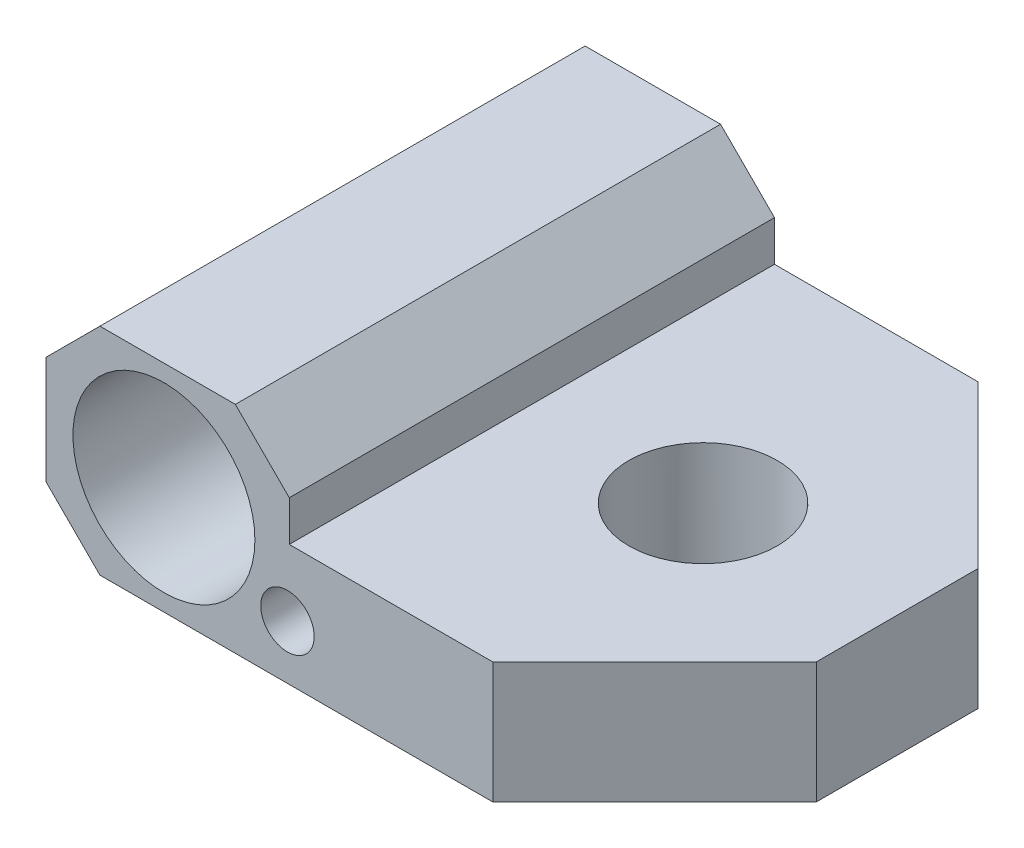
SolidWorks part; units mm, degrees
material "2024 Alloy"
ref_plane "Front Plane" through (0, 0, 0) normal (0, 0, 1) x (1, 0, 0)
ref_plane "Top Plane" through (0, 0, 0) normal (0, 1, 0) x (1, 0, 0)
ref_plane "Right Plane" through (0, 0, 0) normal (1, 0, 0) x (0, 0, -1)
sketch "Sketch1" plane through (0, 0, 0) normal (0, 1, 0) x (1, 0, 0)
  line L0 (0, 0) -> (0, 9) construction
  line L1 (-15.375, 9) -> (7.2, 9)
  line L2 (-15.375, 9) -> (-15.375, -9)
  line L3 (-15.375, -9) -> (7.2, -9)
  line L4 (7.2, 9) -> (7.2, -9)
  line L5 (-11, -9) -> (-11, 9) construction
  line L6 (-14.375, -9) -> (-14.375, 9) construction
  line L7 (-7.625, -9) -> (-7.625, 9) construction
  line L8 (-4, -9) -> (-4, 9) construction
  line L9 (-5.981, -9) -> (-5.981, 9) construction
  line L10 (0, 0) -> (7.2, 0) construction
  line L11 (7.2, 0) -> (3.6, 6.2354) construction
  line L12 (3.6, 6.2354) -> (-3.6, 6.2354) construction
  line L13 (-3.6, 6.2354) -> (-7.2, 0) construction
  line L14 (-7.2, 0) -> (-3.6, -6.2354) construction
  line L15 (-3.6, -6.2354) -> (3.6, -6.2354) construction
  line L16 (3.6, -6.2354) -> (7.2, 0) construction
  circle A0 centre (0, 0) radius 2.75
  circle A1 centre (0, 0) radius 6.2354 construction
  dimension "D1" = 5.5
  dimension "D4" = 14.4
  dimension "D2" = 6.75
  dimension "D3" = 11
  dimension "D5" = 1.981
  dimension "D6" = 1
  dimension "D7" = 18
  dimension "D8" = 4
extrude "Boss-Extrude1" add sketch "Sketch1" along normal blind 4 and the other way blind 4
cosmetic thread "Cosmetic Thread1" parameters "D2"=7.9375
sketch "Sketch3" plane through (0, 0, 9) normal (0, 0, 1) x (1, 0, 0)
  line L2 (-6.4174, -2) -> (-6.4174, -4) construction
  line L3 (-15.375, -4) -> (7.2, -4) construction
  line L4 (-11, 0) -> (-6.4174, -2) construction
  circle A0 centre (-11, 0) radius 3.375
  circle A1 centre (-6.4174, -2) radius 0.9905
  dimension "D1" = 1.981
  dimension "D2" = 2
  dimension "D3" = 5
extrude "Cut-Extrude1" cut sketch "Sketch3" against normal through all
sketch "Sketch4" plane through (0, 0, 9) normal (0, 0, 1) x (1, 0, 0)
  line L0 (0, 0) -> (0, 11.627) construction
  line L1 (7.2, 4) -> (-6.35, 4)
  line L2 (7.2, 4) -> (7.2, 0.5)
  line L3 (7.2, 0.5) -> (-6.35, 0.5)
  line L4 (-6.35, 4) -> (-6.35, 0.5)
  dimension "D1" = 3.5
  dimension "D2" = 12.7
extrude "Cut-Extrude2" cut sketch "Sketch4" against normal through all
sketch "Sketch5" plane through (0, 0.5, 0) normal (0, 1, 0) x (-1, 0, 0)
  line L0 (-1.2, -9) -> (-7.2, -3)
  line L1 (6.35, -9) -> (-7.2, -9) construction
  line L2 (-7.2, -9) -> (-7.2, 9) construction
  line L3 (-1.2, 9) -> (-7.2, 3)
  line L4 (6.35, 9) -> (-7.2, 9) construction
  line L5 (0, 0) -> (-7.2, 0) construction
  line L6 (-1.2, -9) -> (-7.2, -9)
  line L7 (-7.2, -9) -> (-7.2, -3)
  line L8 (-7.2, 3) -> (-7.2, 9)
  line L9 (-7.2, 9) -> (-1.2, 9)
  circle A0 centre (0, 0) radius 7.2 construction
  dimension "D1" = 6
  dimension "D2" = 6
  dimension "D3" = 6
extrude "Cut-Extrude3" cut sketch "Sketch5" against normal through all
chamfer "Chamfer1" distance 2 angle 45 3 edges at (-15.375, -4, 0) (-15.375, 4, 0) (-6.35, 4, 0)
